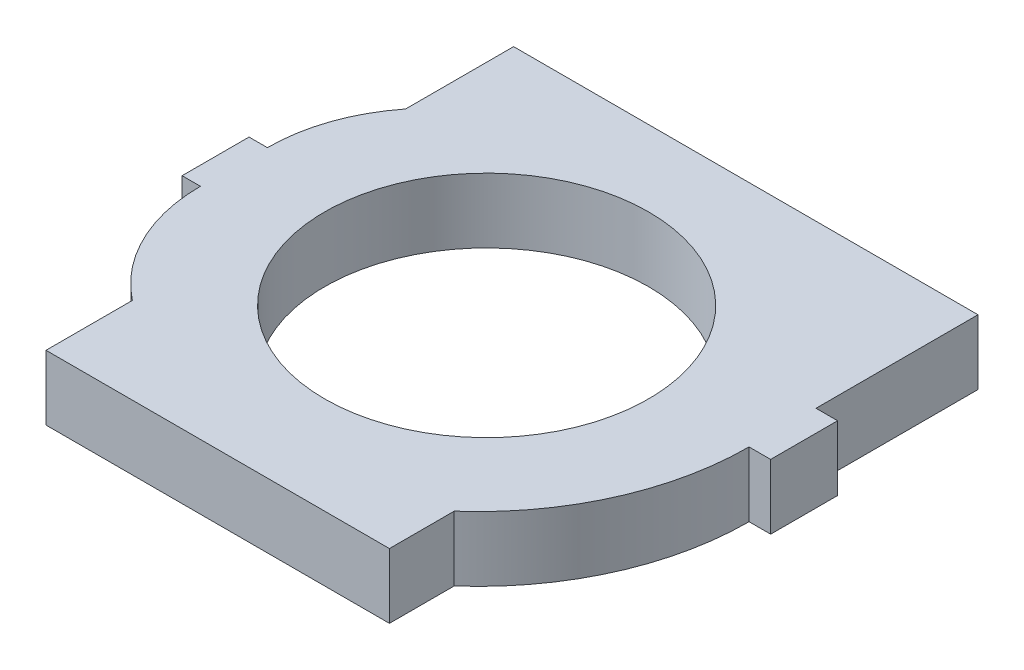
SolidWorks part; units mm, degrees
ref_plane "Front Plane" through (0, 0, 0) normal (0, 0, 1) x (1, 0, 0)
ref_plane "Top Plane" through (0, 0, 0) normal (0, 1, 0) x (1, 0, 0)
ref_plane "Right Plane" through (0, 0, 0) normal (1, 0, 0) x (0, 0, -1)
sketch "Sketch1" plane through (0, 0, 0) normal (0, 1, 0) x (1, 0, 0)
  line L0 (-28.3, -16.2911) -> (-28.3, 16.8497) construction
  line L1 (-28.3, 16.8497) -> (28.3, 16.8497) construction
  line L2 (28.3, 16.8497) -> (28.3, -16.2911) construction
  line L3 (0, 16.8497) -> (0, 0) construction
  line L4 (28.3, 0) -> (-28.3, 0) construction
  line L5 (-31.4, -24.8) -> (31.4, -24.8)
  line L6 (-31.4, 21.2) -> (31.4, 21.2)
  line L7 (-31.4, 21.2) -> (-31.4, -24.8)
  line L8 (31.4, 21.2) -> (31.4, -24.8)
  circle A0 centre (-28.3, -1.4) radius 1.4
  circle A1 centre (28.3, 3.1) radius 1.4
  circle A2 centre (28.3, 3.1) radius 3.1 construction
  circle A3 centre (-28.3, -1.4) radius 3.1 construction
  circle A4 centre (-0.6, -0.8) radius 15
  dimension "D2" = 6.2
  dimension "D3" = 2.8
  dimension "D8" = 30
  dimension "D1" = 56.6
  dimension "D4" = 24.8
  dimension "D5" = 46
  dimension "D6" = 22
  dimension "D7" = 32
extrude "Boss-Extrude1" add sketch "Sketch1" along normal blind 6
sketch "Sketch2" plane through (0, 6, 0) normal (0, 1, 0) x (1, 0, 0)
  line L0 (22.9, 21.2) -> (22.9, 6.2)
  line L1 (31.4, 21.2) -> (-31.4, 21.2) construction
  line L2 (22.9, 6.2) -> (31.4, 6.2)
  line L3 (31.4, -24.8) -> (31.4, 21.2) construction
  line L4 (31.4, 6.2) -> (31.4, 21.2)
  line L5 (31.4, 21.2) -> (22.9, 21.2)
  line L6 (14.4, -24.8) -> (31.4, -24.8)
  line L7 (-31.4, -24.8) -> (31.4, -24.8) construction
  line L8 (31.4, -24.8) -> (31.4, 0)
  line L9 (31.4, 0) -> (22.9, 0)
  line L10 (14.4, -18.8) -> (14.4, -24.8)
  line L11 (-17.4, -24.8) -> (-17.4, -16.8)
  line L12 (-23.4, -4.5) -> (-31.4, -4.5)
  line L13 (-31.4, 21.2) -> (-31.4, -24.8) construction
  line L14 (-31.4, -4.5) -> (-31.4, -24.8)
  line L15 (-31.4, -24.8) -> (-17.4, -24.8)
  line L16 (-23.4, -4.5) -> (-23.4, 13.5193) construction
  line L17 (-20.1, 21.2) -> (-20.1, 11.2)
  line L18 (-20.1, 21.2) -> (-31.4, 21.2)
  line L19 (-31.4, 21.2) -> (-31.4, 1.7)
  line L20 (-31.4, 1.7) -> (-23.4, 1.7)
  circle A0 centre (28.3, 3.1) radius 1.4 construction
  arc A1 (22.9, 0) -> (14.4, -18.8) centre (-2.1406, 0) cw
  arc A2 (-17.4, -16.8) -> (-23.4, -4.5) centre (-7.7925, -4.5) cw
  circle A3 centre (-28.3, -1.4) radius 1.4 construction
  arc A4 (-23.4, 1.7) -> (-20.1, 11.2) centre (-8.0758, 1.7) cw
  dimension "D2" = 3.1
  dimension "D4" = 6
  dimension "D7" = 3.1
  dimension "D1" = 8.5
  dimension "D3" = 17
  dimension "D5" = 8
  dimension "D6" = 14
  dimension "D8" = 8
  dimension "D9" = 43
  dimension "D10" = 10
  dimension "D11" = 3.1
extrude "Cut-Extrude1" cut sketch "Sketch2" against normal through all
fillet "Fillet1" radius 3.1 4 edges at (-31.4, 3, 4.5) (-31.4, 3, -1.7) (31.4, 3, -6.2) (31.4, 3, 0)
sketch "Sketch3" plane through (0, 6, 0) normal (0, 1, 0) x (1, 0, 0)
  line L0 (28.3, 0) -> (22.9, 0) construction
  line L1 (22.9, 6.2) -> (28.3, 6.2) construction
  line L2 (28.3, 0) -> (24.9, 0)
  line L3 (24.9, 6.2) -> (28.3, 6.2)
  line L4 (24.9, 6.2) -> (24.9, 0)
  line L5 (22.9, 21.2) -> (22.9, 6.2) construction
  line L6 (-23.4, -4.5) -> (-28.3, -4.5) construction
  line L7 (-28.3, 1.7) -> (-23.4, 1.7) construction
  line L8 (-25.1, -4.5) -> (-28.3, -4.5)
  line L9 (-28.3, 1.7) -> (-25.1, 1.7)
  line L10 (-25.1, 1.7) -> (-25.1, -4.5)
  arc A0 (28.3, 0) -> (31.4, 3.1) centre (28.3, 3.1) ccw construction
  arc A1 (31.4, 3.1) -> (28.3, 6.2) centre (28.3, 3.1) ccw construction
  arc A2 (28.3, 0) -> (31.4, 3.1) centre (28.3, 3.1) ccw
  arc A3 (31.4, 3.1) -> (28.3, 6.2) centre (28.3, 3.1) ccw
  arc A4 (-31.4, -1.4) -> (-28.3, -4.5) centre (-28.3, -1.4) ccw construction
  arc A5 (-28.3, 1.7) -> (-31.4, -1.4) centre (-28.3, -1.4) ccw construction
  arc A6 (-31.4, -1.4) -> (-28.3, -4.5) centre (-28.3, -1.4) ccw
  arc A7 (-28.3, 1.7) -> (-31.4, -1.4) centre (-28.3, -1.4) ccw
  dimension "D1" = 2
  dimension "D2" = 50
extrude "Cut-Extrude2" cut sketch "Sketch3" against normal through all body kept at (-23.4, 0, 4.5)
